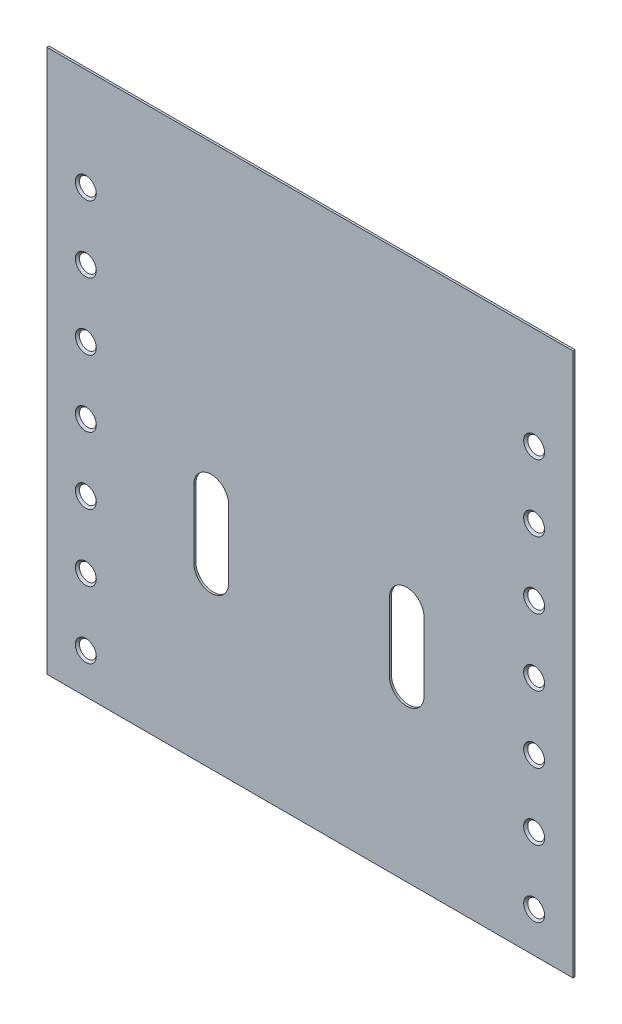
SolidWorks part; units mm, degrees
ref_plane "Front Plane" through (0, 0, 0) normal (0, 0, 1) x (1, 0, 0)
ref_plane "Top Plane" through (0, 0, 0) normal (0, 1, 0) x (1, 0, 0)
ref_plane "Right Plane" through (0, 0, 0) normal (1, 0, 0) x (0, 0, -1)
sketch "Sketch1" plane through (0, 0, 0) normal (0, 0, -1) x (1, 0, 0)
  line L1 (-203.2, 237) -> (-6.35, 237)
  line L2 (-203.2, 237) -> (-203.2, 33.8)
  line L3 (-203.2, 33.8) -> (-6.35, 33.8)
  line L4 (-6.35, 237) -> (-6.35, 33.8)
  dimension "D2" = 196.85
  dimension "D3" = 203.2
extrude "Boss-Extrude1" add sketch "Sketch1" along normal blind 0.7747
sketch "Sketch2" plane through (0, 0, -0.7747) normal (0, 0, -1) x (1, 0, 0)
  line L0 (-141.7213, 180) -> (-141.7213, 141.5) construction
  line L1 (-6.35, 237) -> (-203.2, 237) construction
  line L2 (-141.7213, 180) -> (-141.7213, 237) construction
  line L3 (-141.7213, 173.5) -> (-141.7213, 148) construction
  line L6 (-135.2213, 173.5) -> (-135.2213, 148)
  line L7 (-148.2213, 173.5) -> (-148.2213, 148)
  line L8 (-141.7213, 160.75) -> (-203.2, 160.75) construction
  line L9 (-203.2, 237) -> (-203.2, 33.8) construction
  line L10 (-68.5693, 180) -> (-68.5693, 141.5) construction
  line L11 (-68.5693, 180) -> (-68.5693, 237) construction
  line L12 (-68.5693, 173.5) -> (-68.5693, 148) construction
  line L15 (-141.7213, 160.75) -> (-68.5693, 160.75) construction
  line L16 (-62.0693, 173.5) -> (-62.0693, 148)
  line L17 (-75.0693, 173.5) -> (-75.0693, 148)
  arc A2 (-135.2213, 173.5) -> (-148.2213, 173.5) centre (-141.7213, 173.5) ccw
  arc A3 (-148.2213, 148) -> (-135.2213, 148) centre (-141.7213, 148) ccw
  arc A6 (-62.0693, 173.5) -> (-75.0693, 173.5) centre (-68.5693, 173.5) ccw
  arc A7 (-75.0693, 148) -> (-62.0693, 148) centre (-68.5693, 148) ccw
  point P5 (-141.7213, 160.75)
  point P18 (-68.5693, 160.75)
  dimension "D4" = 6.5
  dimension "D6" = 57
  dimension "D5" = 6.5
  dimension "D1" = 73.152
  dimension "D2" = 57
  dimension "D3" = 38.5
  dimension "D8" = 38.5
extrude "Cut-Extrude7" cut sketch "Sketch2" against normal through all
ref_plane "Plane1" through (-104.775, 0, 0) normal (1, 0, 0) x (0, 0, -1)
sketch "Sketch4" plane through (0, 0, 0) normal (0, 0, 1) x (1, 0, 0)
  line L0 (-203.2, -33.8) -> (-6.35, -33.8) construction
  line L1 (-6.35, -33.8) -> (-203.2, -33.8)
  line L2 (-6.35, -33.8) -> (-6.35, -34.4096)
  line L3 (-6.35, -34.4096) -> (-203.2, -34.4096)
  line L4 (-203.2, -33.8) -> (-203.2, -34.4096)
  line L5 (-6.35, -237) -> (-6.35, 2) construction
  line L6 (-203.2, 2) -> (-203.2, -237) construction
  dimension "D1" = 0.6096
extrude "Boss-Extrude2" add sketch "Sketch4" along normal blind 12
sketch "Sketch8" plane through (0, 0, -0.7747) normal (0, 0, -1) x (-1, 0, 0)
  circle A0 centre (185.47, -222) radius 3.75
  circle A1 centre (185.47, -197) radius 3.75
  circle A2 centre (185.47, -172) radius 3.75
  circle A3 centre (185.47, -147) radius 3.75
  circle A4 centre (185.47, -122) radius 3.75
  circle A5 centre (185.47, -97) radius 3.75
  dimension "D1" = 7.5
sketch "Sketch13" plane through (0, 0, 12) normal (0, 0, 1) x (1, 0, 0)
  line L1 (-6.35, -34.4096) -> (-203.2, -34.4096)
  line L2 (-6.35, -34.4096) -> (-6.35, -33.8)
  line L3 (-6.35, -33.8) -> (-203.2, -33.8)
  line L4 (-203.2, -34.4096) -> (-203.2, -33.8)
sketch "Sketch14" plane through (0, 0, 0) normal (0, 0, 1) x (1, 0, 0)
  line L0 (-6.35, -34.4096) -> (-6.35, -237) construction
  line L1 (-6.35, -59.904) -> (-203.2, -59.904)
  line L2 (-6.35, -59.904) -> (-6.35, -47.966)
  line L3 (-6.35, -47.966) -> (-203.2, -47.966)
  line L4 (-203.2, -59.904) -> (-203.2, -47.966)
  line L5 (-203.2, -237) -> (-203.2, -34.4096) construction
  dimension "D1" = 11.938
extrude "Boss-Extrude3" add sketch "Sketch14" against normal up to surface (0.7747 mm away) up to face at (-141.7213, -160.75, -0.7747)
extrude "Cut-Extrude9" cut sketch "Sketch13" against normal up to surface (12 mm away) up to face at (-68.5693, -160.75, 0)
hole_wizard "CSK for M3 Flat Head Machine Screw3" positions "Sketch15" profile "Sketch16" countersink size "M3" standard "ANSI Metric" end condition through all
sketch "Sketch15" plane through (0, 0, 0) normal (0, 0, 1) x (1, 0, 0)
  point P18 (-188.645, -72)
  point P21 (-188.645, -222)
  point P24 (-188.645, -197)
  point P27 (-188.645, -172)
  point P30 (-188.645, -147)
  point P33 (-188.645, -122)
  point P36 (-188.645, -97)
  point P39 (-188.645, -72)
sketch "Sketch16" plane through (-188.645, -72, 0) normal (1, 0, 0) x (0, -1, 0)
  line L0 (0, 0) -> (0, 0.7747)
  line L1 (0, 0.7747) -> (1.7, 0.7747)
  line L2 (1.7, 0.7747) -> (1.7, 2.212)
  line L3 (1.7, 2.212) -> (3.912, 0)
  line L5 (3.912, 0) -> (0, 0)
  line L6 (-1.7, 2.212) -> (-3.912, 0) construction
  line L11 (0, -6.35) -> (0, 107.95) construction
  dimension "Thru Hole Dia." = 3.4
  dimension "Thru Hole Depth" = 0.7747
  dimension "Near C'Sink Dia." = 7.824
  dimension "Near C'Sink Angle" = 90
ref_plane "Plane2" through (-104.775, 0, 0) normal (1, 0, 0) x (0, 0, -1)
mirror "Mirror1" about plane through (-104.775, 0, 0) normal (1, 0, 0) of "CSK for M3 Flat Head Machine Screw3"
sketch "Sketch17" plane through (0, 0, -0.7747) normal (0, 0, -1) x (-1, 0, 0)
  line L0 (62.0693, -148) -> (62.0693, -173.5) construction
  point P8 (141.7213, -160.75)
  point P17 (68.5693, -160.75)
  dimension "D1" = 6.5
  dimension "D2" = 79.652
  dimension "D3" = 12.75
